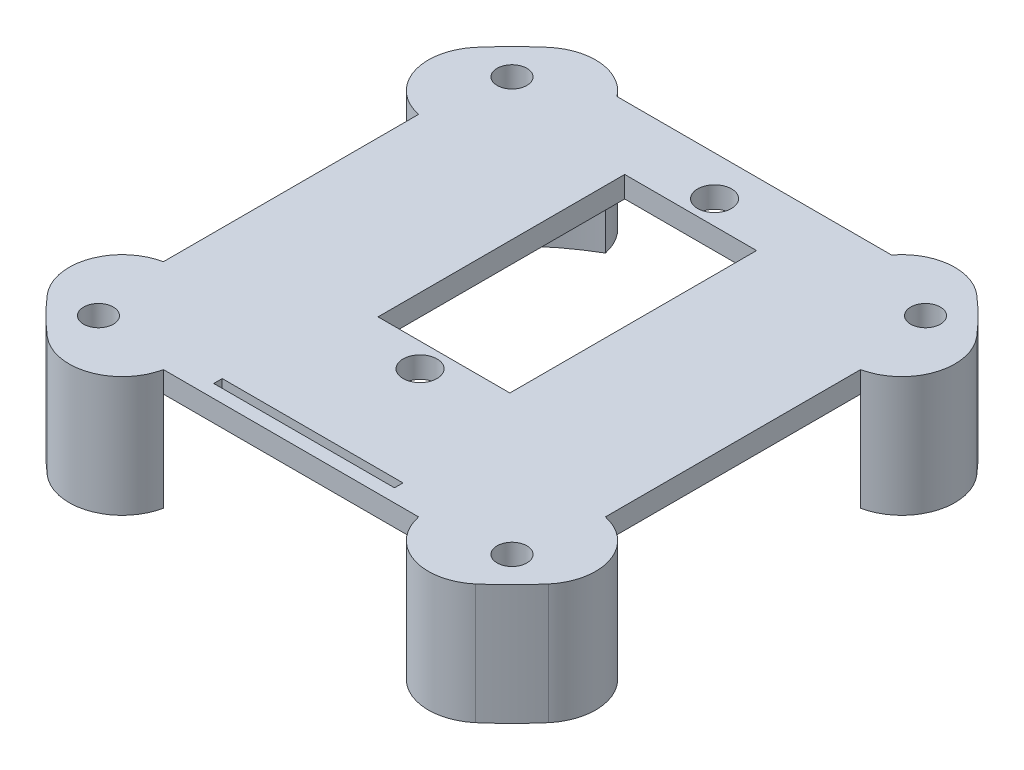
SolidWorks part; units mm, degrees
material "Nylon 101 90%"
ref_plane "Front Plane" through (0, 0, 0) normal (0, 0, 1) x (1, 0, 0)
ref_plane "Top Plane" through (0, 0, 0) normal (0, 1, 0) x (1, 0, 0)
ref_plane "Right Plane" through (0, 0, 0) normal (1, 0, 0) x (0, 0, -1)
sketch "Sketch2" plane through (0, 0, 0) normal (0, 1, 0) x (1, 0, 0)
  circle A0 centre (0, 0) radius 16.7505 construction
  circle A1 centre (0, 0) radius 16.7505
  circle A2 centre (19.4454, -19.4454) radius 1.6 construction
  circle A3 centre (19.4454, -19.4454) radius 1.6
  circle A4 centre (19.4454, 19.4454) radius 1.6 construction
  circle A5 centre (19.4454, 19.4454) radius 1.6
  circle A6 centre (-19.4454, 19.4454) radius 1.6 construction
  circle A7 centre (-19.4454, 19.4454) radius 1.6
  circle A8 centre (-19.4454, -19.4454) radius 1.6 construction
  circle A9 centre (-19.4454, -19.4454) radius 1.6
sketch "Sketch3" plane through (0, 0, 0) normal (0, 1, 0) x (1, 0, 0)
  line L0 (-0.45, 21.25) -> (-5.8, 21.25) construction
  line L1 (-0.45, 21.25) -> (-5.8, 21.25) construction
  line L2 (-5.8, -10.85) -> (-0.45, -10.85) construction
  line L3 (-5.8, -10.85) -> (-0.45, -10.85) construction
  line L4 (-6.2, 16.1) -> (-6.2, 2.2271) construction
  line L5 (-6.2, 16.1) -> (-6.2, 2.2271)
  line L6 (6.2, 2.2271) -> (6.2, 16.1) construction
  line L7 (6.2, 2.2271) -> (6.2, 16.1)
  line L8 (-5.7, -6.4) -> (5.7, -6.4) construction
  line L9 (-5.7, -6.4) -> (5.7, -6.4)
  line L10 (5.7, 16.8) -> (-5.7, 16.8) construction
  line L11 (5.7, 16.8) -> (-5.7, 16.8)
  line L12 (0, 0) -> (19.4454, -19.4454) construction
  line L13 (19.4454, -19.4454) -> (21.9203, -21.9203) construction
  line L18 (0, 0) -> (0, 31) construction
  line L19 (-6.2, 2.2271) -> (-6.2, -6.4)
  line L20 (-6.2, -6.4) -> (-5.7, -6.4)
  line L21 (6.2, 2.2271) -> (6.2, -6.4)
  line L22 (6.2, -6.4) -> (5.7, -6.4)
  line L23 (5.7, 16.8) -> (6.2, 16.8)
  line L24 (6.2, 16.8) -> (6.2, 16.1)
  line L25 (-5.7, 16.8) -> (-6.2, 16.8)
  line L26 (-6.2, 16.8) -> (-6.2, 16.1)
  arc A0 (0.352, -9.2765) -> (-0.352, -9.2765) centre (0, -8.65) ccw construction
  arc A1 (0.352, -9.2765) -> (-0.352, -9.2765) centre (0, -8.65) ccw construction
  arc A2 (-0.3628, 19.799) -> (0.3628, 19.799) centre (0, 19.05) ccw construction
  arc A3 (-0.3628, 19.799) -> (0.3628, 19.799) centre (0, 19.05) ccw construction
  circle A4 centre (0, 0) radius 31
  circle A5 centre (0, -8.65) radius 1.6
  circle A6 centre (0, 19.05) radius 1.6
  dimension "D4" = 3.2
  dimension "D1" = 3.5
extrude "Servo mount" add sketch "Sketch3" against normal blind 2
sketch "Sketch4" plane through (0, -2, 0) normal (0, -1, 0) x (-1, 0, 0)
  line L0 (-19.4454, -19.4454) -> (-16.9706, -16.9706) construction
  line L1 (0, 0) -> (-19.4454, -19.4454) construction
  line L2 (-19.4454, -19.4454) -> (-21.9203, -21.9203) construction
  circle A1 centre (0, 0) radius 31
  circle A2 centre (0, 0) radius 31
  circle A4 centre (-19.4454, -19.4454) radius 1.6 construction
  circle A5 centre (-19.4454, -19.4454) radius 1.6 construction
  circle A12 centre (0, 0) radius 24
  dimension "D1" = 0
extrude "Spacer" add sketch "Sketch4" along normal up to surface (9.3 mm away)
sketch "Sketch10" plane through (0, -11.3, 0) normal (0, -1, 0) x (1, 0, 0)
  circle A0 centre (-19.4454, -19.4454) radius 1.4
  circle A1 centre (19.4454, -19.4454) radius 1.4
  circle A2 centre (-19.4454, 19.4454) radius 1.4
  circle A3 centre (19.4454, 19.4454) radius 1.4
  dimension "D1" = 2.8
sketch "Sketch5" plane through (0, 0, 0) normal (0, 1, 0) x (1, 0, 0)
  line L0 (-8.5, -19.5505) -> (8.5, -19.5505) construction
  line L1 (-8.5, -19.5505) -> (8.5, -19.5505)
  line L2 (8.5, -18.7505) -> (-8.5, -18.7505) construction
  line L3 (8.5, -18.7505) -> (-8.5, -18.7505)
  line L4 (8.5, -19.5505) -> (8.5, -18.7505) construction
  line L5 (8.5, -19.5505) -> (8.5, -18.7505)
  line L6 (-8.5, -18.7505) -> (-8.5, -19.5505) construction
  line L7 (-8.5, -18.7505) -> (-8.5, -19.5505)
extrude "Flex cable" cut sketch "Sketch5" against normal up to next
sketch "Sketch7" plane through (0, -2, 0) normal (0, -1, 0) x (1, 0, 0)
  line L0 (0, 0) -> (0, -31) construction
  line L3 (-12, -31) -> (12, -31)
  line L4 (-12, -31) -> (-12, 31)
  line L5 (-12, 31) -> (12, 31)
  line L6 (12, -31) -> (12, 31)
  line L7 (-12, -31) -> (12, 31) construction
  line L8 (-12, 31) -> (12, -31) construction
  circle A0 centre (0, 0) radius 31 construction
  dimension "D1" = 24
extrude "Cut-Extrude3" cut sketch "Sketch7" along normal through all
sketch "Sketch8" plane through (0, -2, 0) normal (0, -1, 0) x (1, 0, 0)
  line L1 (-31, 12) -> (31, 12)
  line L2 (-31, 12) -> (-31, -12)
  line L3 (-31, -12) -> (31, -12)
  line L4 (31, 12) -> (31, -12)
  line L5 (-31, 12) -> (31, -12) construction
  line L6 (-31, -12) -> (31, 12) construction
  circle A0 centre (0, 0) radius 31 construction
  point P0 (0, 0)
  dimension "D1" = 24
extrude "Cut-Extrude4" cut sketch "Sketch8" along normal through all
extrude "Mounting holes" cut sketch "Sketch10" against normal up to next
sketch "Sketch11" plane through (0, -2, 0) normal (0, -1, 0) x (1, 0, 0)
  line L0 (-12, -22.7846) -> (12, -22.7846)
  line L6 (12, 20.7846) -> (12, 28.5832) construction
  line L7 (28.5832, 12) -> (20.7846, 12) construction
  line L8 (20.7846, -12) -> (28.5832, -12) construction
  line L9 (12, -28.5832) -> (12, -20.7846) construction
  line L10 (-12, -20.7846) -> (-12, -28.5832) construction
  line L11 (-28.5832, -12) -> (-20.7846, -12) construction
  line L12 (-20.7846, 12) -> (-28.5832, 12) construction
  line L13 (-12, 28.5832) -> (-12, 20.7846) construction
  line L14 (28.5832, 12) -> (20.7846, 12)
  line L15 (20.7846, -12) -> (28.5832, -12)
  line L16 (12, -28.5832) -> (12, -22.7846)
  line L17 (-12, -22.7846) -> (-12, -28.5832)
  line L18 (-28.5832, -12) -> (-20.7846, -12)
  line L19 (-20.7846, 12) -> (-28.5832, 12)
  line L20 (12, 20.7846) -> (12, 28.5832)
  line L21 (-12, 28.5832) -> (-12, 20.7846)
  line L22 (-12, 20.7846) -> (12, 20.7846)
  line L23 (20.7846, 12) -> (20.7846, -12)
  line L24 (12, -20.7846) -> (-12, -20.7846) construction
  line L25 (-20.7846, -12) -> (-20.7846, 12)
  arc A0 (12, 28.5832) -> (-12, 28.5832) centre (0, 0) ccw construction
  arc A1 (12, 28.5832) -> (-12, 28.5832) centre (0, 0) ccw
  arc A2 (28.5832, -12) -> (28.5832, 12) centre (0, 0) ccw construction
  arc A3 (-28.5832, 12) -> (-28.5832, -12) centre (0, 0) ccw construction
  arc A4 (-12, -28.5832) -> (12, -28.5832) centre (0, 0) ccw construction
  arc A5 (28.5832, -12) -> (28.5832, 12) centre (0, 0) ccw
  arc A6 (-28.5832, 12) -> (-28.5832, -12) centre (0, 0) ccw
  arc A7 (-12, -28.5832) -> (12, -28.5832) centre (0, 0) ccw
  dimension "D1" = 2
extrude "Cut-Extrude5" cut sketch "Sketch11" against normal up to next
fillet "Fillet2" radius 5 8 edges at (12, -5.65, -28.5832) (-28.5832, -5.65, -12) (-28.5832, -5.65, 12) (28.5832, -5.65, 12) (12, -5.65, 28.5832) (-12, -5.65, 28.5832) (-12, -5.65, -28.5832) (28.5832, -5.65, -12)
